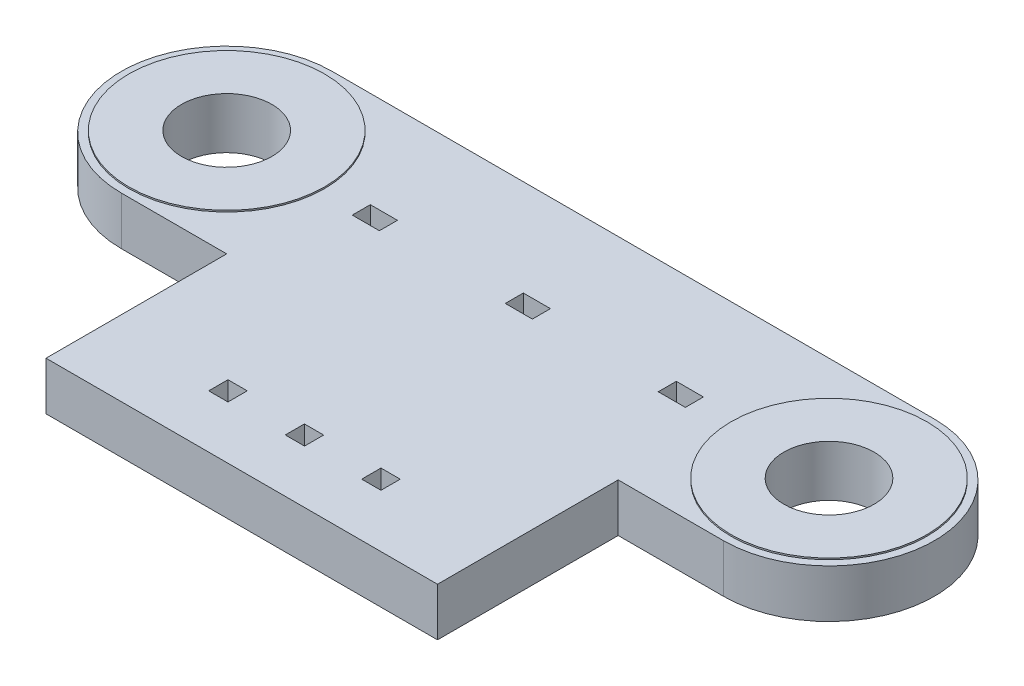
SolidWorks part; units mm, degrees
ref_plane "Front Plane" through (0, 0, 0) normal (0, 0, 1) x (1, 0, 0)
ref_plane "Top Plane" through (0, 0, 0) normal (0, 1, 0) x (1, 0, 0)
ref_plane "Right Plane" through (0, 0, 0) normal (1, 0, 0) x (0, 0, -1)
sketch "Sketch1" plane through (0, 0, 0) normal (0, 1, 0) x (1, 0, 0)
  line L0 (0, 97.8774) -> (0, -75.4137) construction
  line L1 (-187.1972, 0) -> (25.8529, 0) construction
  line L2 (-10, 3.5) -> (10, 3.5)
  line L3 (6.5, -9.5) -> (-6.5, -9.5)
  line L4 (-6.5, -9.5) -> (-6.5, -3.5)
  line L5 (-10, -3.5) -> (-6.5, -3.5)
  line L6 (10, -3.5) -> (6.5, -3.5)
  line L7 (6.5, -9.5) -> (6.5, -3.5)
  arc A0 (-10, 3.5) -> (-10, -3.5) centre (-10, 0) ccw
  circle A1 centre (-10, 0) radius 1.5
  arc A2 (10, 3.5) -> (10, -3.5) centre (10, 0) cw
  circle A3 centre (10, 0) radius 1.5
  point P18 (0, 3.5)
  point P20 (0, -9.5)
  dimension "D1" = 7
  dimension "D3" = 3
  dimension "D2" = 20
  dimension "D4" = 13
  dimension "D5" = 13
extrude "Boss-Extrude1" add sketch "Sketch1" along normal blind 0.8 and the other way blind 0.8
sketch "Sketch4" plane through (0, 0.8, 0) normal (0, 1, 0) x (1, 0, 0)
  line L0 (0, 3.5) -> (0, -9.5) construction
  line L1 (10, 3.5) -> (-10, 3.5) construction
  line L2 (-6.5, -9.5) -> (6.5, -9.5) construction
  circle A4 centre (10, 0) radius 1.5
  circle A5 centre (10, 0) radius 1.5
  circle A6 centre (-10, 0) radius 3.25
  circle A7 centre (-10, 0) radius 1.5
  circle A8 centre (-10, 0) radius 1.5
  circle A9 centre (10, 0) radius 3.25
  dimension "D3" = 6.5
  dimension "D1" = 0
  dimension "D2" = 0
extrude "Boss-Extrude4" add sketch "Sketch4" along normal blind 0.05
mirror "Mirror1" about plane through (0, 0, 0) normal (0, 1, 0) of "Boss-Extrude4"
sketch "Sketch5" plane through (0, 0.8, 0) normal (0, 1, 0) x (1, 0, 0)
  line L0 (0, 3.5) -> (0, -9.5) construction
  line L1 (10, 3.5) -> (-10, 3.5) construction
  line L2 (-6.5, -9.5) -> (6.5, -9.5) construction
  line L3 (-6.5, -7.4175) -> (6.5, -7.4175) construction
  line L4 (-0.32, -7.735) -> (0.32, -7.735)
  line L5 (-0.32, -7.735) -> (-0.32, -7.1)
  line L6 (-0.32, -7.1) -> (0.32, -7.1)
  line L7 (0.32, -7.735) -> (0.32, -7.1)
  line L8 (-0.32, -7.735) -> (0.32, -7.1) construction
  line L9 (-0.32, -7.1) -> (0.32, -7.735) construction
  line L10 (-6.5, -3.5) -> (-6.5, -9.5) construction
  line L11 (6.5, -9.5) -> (6.5, -3.5) construction
  line L12 (-2.22, -7.0975) -> (-2.86, -7.0975)
  line L13 (2.22, -7.7375) -> (2.86, -7.7375)
  line L14 (2.22, -7.7375) -> (2.22, -7.0975)
  line L15 (2.22, -7.0975) -> (2.86, -7.0975)
  line L16 (2.86, -7.7375) -> (2.86, -7.0975)
  line L17 (2.22, -7.7375) -> (2.86, -7.0975) construction
  line L18 (2.22, -7.0975) -> (2.86, -7.7375) construction
  line L19 (-2.86, -7.7375) -> (-2.86, -7.0975)
  line L20 (-2.22, -7.7375) -> (-2.86, -7.7375)
  line L21 (-2.22, -7.7375) -> (-2.22, -7.0975)
  line L22 (-2.22, -7.0975) -> (-2.86, -7.7375) construction
  line L23 (-2.22, -7.7375) -> (-2.86, -7.0975) construction
  point P6 (0, -7.4175)
  point P17 (2.54, -7.4175)
  point P26 (0.32, -7.74)
  point P27 (0.32, -7.7012)
  dimension "D1" = 0.64
  dimension "D2" = 2.4
  dimension "D3" = 2.54
  dimension "D4" = 0.635
extrude "Cut-Extrude1" cut sketch "Sketch5" against normal up to surface (1.6 mm away) up to face at (10, -0.8, -3.25)
sketch "Sketch6" plane through (0, 0.8, 0) normal (0, 1, 0) x (1, 0, 0)
  line L0 (-13.5, 0) -> (13.5, 0) construction
  line L1 (0, 2.9) -> (0, -2.9) construction
  line L2 (-6.4, -2.9) -> (6.4, -2.9) construction
  line L3 (-6.4, -2.9) -> (-6.4, 2.9) construction
  line L4 (-6.4, 2.9) -> (6.4, 2.9) construction
  line L5 (6.4, -2.9) -> (6.4, 2.9) construction
  line L6 (-6.4, -2.9) -> (6.4, 2.9) construction
  line L7 (-6.4, 2.9) -> (6.4, -2.9) construction
  line L8 (-0.45, -0.3) -> (0.45, -0.3)
  line L9 (-0.45, -0.3) -> (-0.45, 0.3)
  line L10 (-0.45, 0.3) -> (0.45, 0.3)
  line L11 (0.45, -0.3) -> (0.45, 0.3)
  line L12 (-0.45, -0.3) -> (0.45, 0.3) construction
  line L13 (-0.45, 0.3) -> (0.45, -0.3) construction
  line L14 (-5.53, -0.3) -> (-4.63, -0.3)
  line L15 (-5.53, -0.3) -> (-5.53, 0.3)
  line L16 (-5.53, 0.3) -> (-4.63, 0.3)
  line L17 (-4.63, -0.3) -> (-4.63, 0.3)
  line L18 (-5.53, -0.3) -> (-4.63, 0.3) construction
  line L19 (-5.53, 0.3) -> (-4.63, -0.3) construction
  line L20 (5.53, -0.3) -> (4.63, 0.3) construction
  line L21 (5.53, 0.3) -> (4.63, -0.3) construction
  line L22 (5.53, 0.3) -> (4.63, 0.3)
  line L23 (4.63, -0.3) -> (4.63, 0.3)
  line L24 (5.53, -0.3) -> (4.63, -0.3)
  line L25 (5.53, -0.3) -> (5.53, 0.3)
  arc A0 (-10, 3.5) -> (-10, -3.5) centre (-10, 0) ccw construction
  arc A1 (10, -3.5) -> (10, 3.5) centre (10, 0) ccw construction
  point P8 (0, 0)
  point P14 (0, 0)
  point P19 (-5.08, 0)
  dimension "D1" = 5.8
  dimension "D2" = 12.8
  dimension "D3" = 0.9
  dimension "D4" = 0.6
  dimension "D5" = 5.08
extrude "Cut-Extrude2" cut sketch "Sketch6" against normal up to surface (1.6 mm away) up to face at (-2.54, -0.8, 7.4175)
